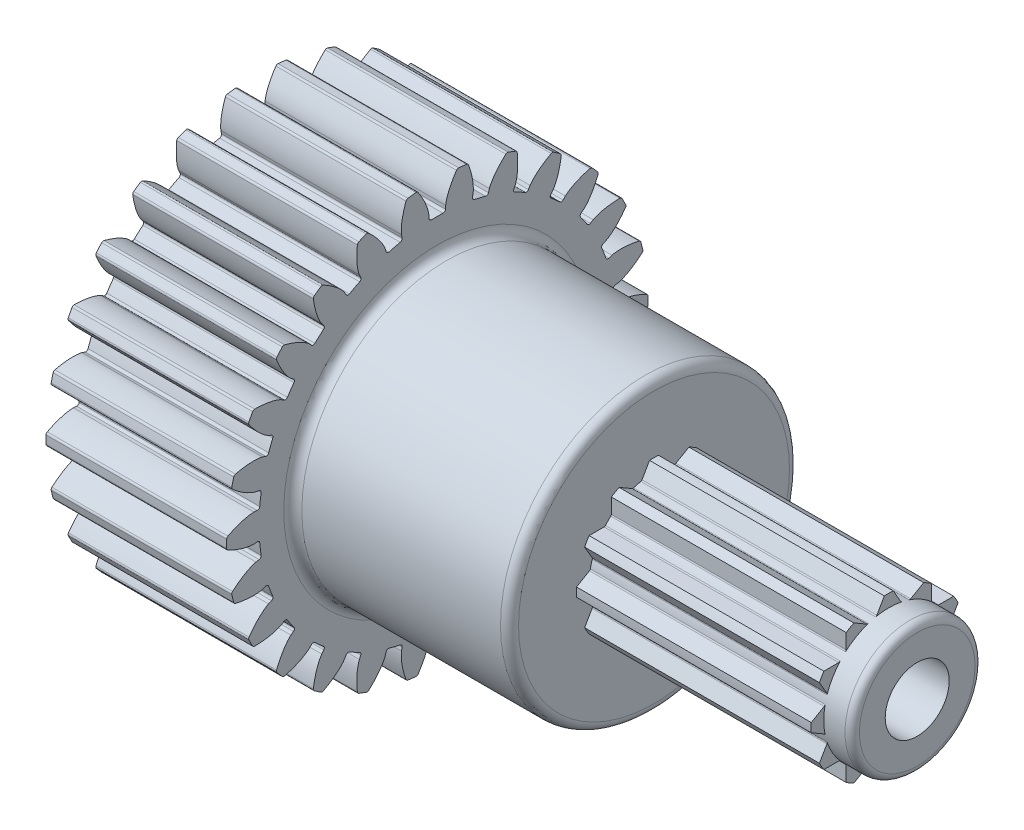
SolidWorks part; units mm, degrees
ref_plane "Front Plane" through (0, 0, 0) normal (1, 0, 0) x (0, 1, 0)
ref_plane "Top Plane" through (0, 0, 0) normal (0, 0, 1) x (0, 1, 0)
ref_plane "Right Plane" through (0, 0, 0) normal (0, 1, 0) x (-1, 0, 0)
sketch "Sketch2" plane through (0, 0, 0) normal (1, 0, 0) x (0, 1, 0)
  circle A0 centre (0, 0) radius 3.9688
  circle A1 centre (0, 0) radius 14.8167
  dimension "D1" = 7.9375
  dimension "D2" = 29.6333
extrude "Gear Width Extrude" add sketch "Sketch2" along normal blind 12.7
sketch "Sketch3" plane through (0, 0, 0) normal (1, 0, 0) x (0, 1, 0)
  line L0 (-14.8167, 0) -> (14.8167, 0) construction
  line L1 (0, 14.8167) -> (0, -14.8167) construction
  line L2 (0, 0) -> (12.9152, 0.5882) construction
  line L5 (12.5338, 0) -> (14.8167, 0)
  line L6 (12.9152, 0.5882) -> (12.5209, 0.5702)
  circle A0 centre (0, 0) radius 12.5338 construction
  circle A1 centre (0, 0) radius 12.9286 construction
  circle A2 centre (0, 0) radius 13.7583 construction
  circle A3 centre (0, 0) radius 14.8167 construction
  arc A7 (14.7499, 1.4052) -> (14.8167, 0) centre (0, 0) cw
  arc A8 (12.5209, 0.5702) -> (12.5338, 0) centre (0, 0) cw
  spline S0 degree 4 poles (12.9152, 0.5882) (12.9182, 0.5884) (12.9266, 0.589) (12.9524, 0.5915) (13.0033, 0.5985) (13.0658, 0.61) (13.1375, 0.6259) (13.2064, 0.6434) (13.2652, 0.6597) (13.3236, 0.6772) (13.3817, 0.6958) (13.4518, 0.7196) (13.5357, 0.7499) (13.6332, 0.788) (13.7433, 0.8343) (13.8548, 0.8849) (13.9641, 0.9373) (14.0738, 0.9935) (14.1795, 1.05) (14.2886, 1.1119) (14.389, 1.1707) (14.5005, 1.2401) (14.5903, 1.2971) (14.7079, 1.376) (14.777, 1.4237) (14.8576, 1.4809) (14.8932, 1.5069) (14.9151, 1.5229) knots 0 0 0 0 0 0.005377 0.015084 0.04661 0.092111 0.119476 0.146842 0.174209 0.201575 0.228941 0.256307 0.307035 0.361767 0.4165 0.471232 0.525964 0.580697 0.635429 0.690161 0.744894 0.799626 0.854358 0.909091 0.954545 1 1 1 1 1 construction
  spline S1 degree 4 poles (12.9152, 0.5882) (12.9182, 0.5884) (12.9266, 0.589) (12.9524, 0.5915) (13.0033, 0.5985) (13.0658, 0.61) (13.1375, 0.6259) (13.2064, 0.6434) (13.2652, 0.6597) (13.3236, 0.6772) (13.3817, 0.6958) (13.4518, 0.7196) (13.5357, 0.7499) (13.6332, 0.788) (13.7433, 0.8343) (13.8548, 0.8849) (13.9641, 0.9373) (14.0738, 0.9935) (14.1795, 1.05) (14.2886, 1.1119) (14.389, 1.1707) (14.5005, 1.2401) (14.5903, 1.2971) (14.6824, 1.3589) (14.7271, 1.3894) (14.7499, 1.4052) knots 0 0 0 0 0 0.005377 0.015084 0.04661 0.092111 0.119476 0.146842 0.174209 0.201575 0.228941 0.256307 0.307035 0.361767 0.4165 0.471232 0.525964 0.580697 0.635429 0.690161 0.744894 0.799626 0.854358 0.909091 0.909091 0.909091 0.909091 0.909091
  dimension "D1" = 27.5167
  dimension "D2" = 25.8572
  dimension "D3" = 25.0677
extrude "Gear Tooth Cut" cut sketch "Sketch3" along normal blind 25.4
mirror "Gear Tooth Cut Mirror" about plane through (25.4, 0, 0) normal (0, 0, 1) of "Gear Tooth Cut"
fillet "Tooth Fillets" radius 0.1662 4 edges at (6.35, 14.7499, 1.4052) (6.35, 14.7499, -1.4052) (6.35, 12.5209, 0.5702) (6.35, 12.5209, -0.5702)
pattern_circular "CirPattern1" count 26 over 360 about axis through (0, 0, 0) along (1, 0, 0) of "Gear Tooth Cut", "Gear Tooth Cut Mirror", "Tooth Fillets"
sketch "Sketch4" plane through (0, 0, 0) normal (0, 1, 0) x (-1, 0, 0)
  line L5 (0, 0) -> (0, 3.9688)
  line L6 (0, 3.9688) -> (-12.7, 3.9687)
  line L7 (-12.7, 3.9687) -> (-12.7, 10.16)
  line L9 (-44.45, 5.461) -> (-44.45, 0)
  line L10 (6.985, 0) -> (-6.985, 0) construction
  line L11 (-44.45, 0) -> (0, 0)
  line L12 (0, 16.2151) -> (0, -16.2151) construction
  line L13 (-12.7, 3.9688) -> (-12.7, -3.9688) construction
  line L14 (-27.94, 10.16) -> (-27.94, 5.461)
  line L15 (-27.94, 5.461) -> (-44.45, 5.461)
  line L16 (-12.7, 10.16) -> (-27.94, 10.16)
  point P0 (0, 3.9688)
  point P1 (-17.6617, 0)
  point P3 (0, 0)
  point P4 (-0.3557, 0)
  point P10 (0, 0)
  point P21 (0, 0)
  point P22 (0, 0)
  point P23 (4.5864, 0)
  point P24 (3.81, 0)
  point P25 (0, 0)
  point P26 (3.81, 0)
  dimension "D2" = 44.45
  dimension "D3" = 10.16
  dimension "D4" = 5.461
  dimension "D5" = 16.51
revolve "Revolve1" add sketch "Sketch4" angle 360 about L11
sketch "Sketch5" plane through (44.45, 0, 0) normal (1, 0, 0) x (0, 1, 0)
  line L0 (0, 5.461) -> (0, 4.572)
  line L2 (-2.9972, 4.565) -> (-2.9972, 3.4525)
  line L3 (2.9972, 4.565) -> (2.9972, 3.4525)
  line L4 (-2.9972, 8.6613) -> (-2.9972, 5.4085) construction
  line L5 (0, 8.6613) -> (0, 5.4085) construction
  line L6 (2.9972, 8.6613) -> (2.9972, 5.4085) construction
  line L7 (2.7305, 4.7294) -> (2.286, 3.9595)
  line L8 (-0.3131, 5.452) -> (-0.8694, 4.4886)
  line L9 (4.8782, 2.4548) -> (4.3219, 1.4914)
  line L10 (4.7294, 2.7305) -> (3.9595, 2.286)
  line L11 (2.4548, 4.8782) -> (1.4914, 4.3219)
  line L12 (5.452, -0.3131) -> (4.4886, -0.8694)
  line L13 (5.461, 0) -> (4.572, 0)
  line L14 (4.565, 2.9972) -> (3.4525, 2.9972)
  line L15 (4.565, -2.9972) -> (3.4525, -2.9972)
  line L16 (4.7294, -2.7305) -> (3.9595, -2.286)
  line L17 (5.452, 0.3131) -> (4.4886, 0.8694)
  line L18 (2.4548, -4.8782) -> (1.4914, -4.3219)
  line L19 (2.7305, -4.7294) -> (2.286, -3.9595)
  line L20 (4.8782, -2.4548) -> (4.3219, -1.4914)
  line L21 (-0.3131, -5.452) -> (-0.8694, -4.4886)
  line L22 (0, -5.461) -> (0, -4.572)
  line L23 (2.9972, -4.565) -> (2.9972, -3.4525)
  line L24 (-2.9972, -4.565) -> (-2.9972, -3.4525)
  line L25 (-2.7305, -4.7294) -> (-2.286, -3.9595)
  line L26 (0.3131, -5.452) -> (0.8694, -4.4886)
  line L27 (-4.8782, -2.4548) -> (-4.3219, -1.4914)
  line L28 (-4.7294, -2.7305) -> (-3.9595, -2.286)
  line L29 (-2.4548, -4.8782) -> (-1.4914, -4.3219)
  line L30 (-5.452, 0.3131) -> (-4.4886, 0.8694)
  line L31 (-5.461, 0) -> (-4.572, 0)
  line L32 (-4.565, -2.9972) -> (-3.4525, -2.9972)
  line L33 (-4.565, 2.9972) -> (-3.4525, 2.9972)
  line L34 (-4.7294, 2.7305) -> (-3.9595, 2.286)
  line L35 (-5.452, -0.3131) -> (-4.4886, -0.8694)
  line L36 (-2.4548, 4.8782) -> (-1.4914, 4.3219)
  line L37 (-2.7305, 4.7294) -> (-2.286, 3.9595)
  line L38 (-4.8782, 2.4548) -> (-4.3219, 1.4914)
  line L39 (0.3131, 5.452) -> (0.8694, 4.4886)
  circle A0 centre (0, 0) radius 5.461
  circle A1 centre (0, 0) radius 4.572
  circle A2 centre (0, 0) radius 5.461 construction
  circle A3 centre (0, 0) radius 5.5
  point P111 (0, 0)
  dimension "D1" = 9.144
  dimension "D2" = 2.9972
  dimension "D3" = 2.9972
  dimension "D4" = 12
extrude "Cut-Extrude1" cut sketch "Sketch5" along direction (-1, 0, 0) on the side against the normal up to surface (16.51 mm away) contours A1 L8 L4 L3 | A1 L11 L4 L9 | A1 L14 L4 L12 | A1 L17 L4 L15 | A1 L20 L4 L18 | A1 L23 L4 L21 | A1 L26 L4 L24 | A1 L29 L4 L27 | A1 L32 L4 L30 | A1 L35 L4 L33 | A1 L38 L4 L36 | A1 L2 L4 L39
fillet "Fillet3" radius 0.635 2 edges at (12.7, 0, -10.16) (27.94, 0, -10.16)
fillet "Fillet5" radius 0.127 24 edges at (36.195, -0.8694, 4.4886) (36.195, 1.4914, 4.3219) (36.195, 2.9972, 3.4525) (36.195, 4.3219, 1.4914) (36.195, 3.4525, 2.9972) (36.195, 4.4886, 0.8694) (36.195, 4.4886, -0.8694) (36.195, 3.4525, -2.9972) (36.195, 4.3219, -1.4914) (36.195, 1.4914, -4.3219) (36.195, 2.9972, -3.4525) (36.195, 0.8694, -4.4886) (36.195, -1.4914, -4.3219) (36.195, -3.4525, -2.9972) (36.195, -3.4525, 2.9972) (36.195, -0.8694, -4.4886) (36.195, -2.9972, -3.4525) (36.195, -4.3219, -1.4914) (36.195, -4.4886, 0.8694) (36.195, -4.4886, -0.8694) (36.195, -1.4914, 4.3219) (36.195, 0.8694, 4.4886) (36.195, -4.3219, 1.4914) (36.195, -2.9972, 3.4525)
sketch "Sketch6" plane through (44.45, 0, 0) normal (1, 0, 0) x (0, 0, -1)
  circle A0 centre (0, 0) radius 4.572
extrude "Boss-Extrude1" add sketch "Sketch6" along normal blind 2
fillet "Fillet6" radius 0.508 1 edges at (46.45, 0, -4.572)
sketch "Sketch7" plane through (0, 0, 0) normal (-1, 0, 0) x (0, -1, 0)
  circle A0 centre (0, 0) radius 2.25
  dimension "D1" = 4.5
extrude "Cut-Extrude2" cut sketch "Sketch7" against normal through all contours A0
sketch "Sketch8" plane through (0, 0, 0) normal (-1, 0, 0) x (0, -1, 0)
  circle A0 centre (0, 0) radius 4
  dimension "D1" = 8
extrude "Cut-Extrude3" cut sketch "Sketch8" against normal blind 6.35 contours A0
equation "\"DP\"= 24'INPUT: Diametral Pitch"
equation "\"a_Pressure\"= 20'INPUT: Pressure Angle"
equation "\"Z\"= 26'INPUT: Number of Teeth"
equation "\"w_Face\"= 0.5'INPUT: Face Width"
equation "\"d_Bore\"= 5 / 16'INPUT: Bore Diameter"
equation "\"d_Pitch\"= \"Z\" / \"DP\"'Pitch Diameter"
equation "\"Module\"= 1 / \"DP\"'Module"
equation "\"d_Base\"= \"d_Pitch\" * cos ( \"a_Pressure\" )'Base Circle Diameter"
equation "\"Clearance\"= 0.157 / \"DP\"'Clearance"
equation "\"CP\"= pi * \"d_Pitch\" / \"Z\"'Circular Pitch"
equation "\"h_Addendum\"= 1 / \"DP\"'Addendum Depth"
equation "\"h_Dedendum\"= IIF ( \"h_deStandard\" > \"h_deMin\" , \"h_deStandard\" , \"h_deMin\" )'Dedendum Depth"
equation "\"d_Addendum\"= \"d_Pitch\" + ( 2 * \"h_Addendum\" )'Addendum (Tip) Diameter"
equation "\"d_Dedendum\"= \"d_Pitch\" - ( 2 * \"h_Dedendum\" )'Dedendum (Root) Diameter"
equation "\"a_Pitch\"= 360 / \"Z\"'Pitch Angle"
equation "\"a_Alpha\"= ( ( 180 * ( ( \"d_Pitch\" ^ 2 ) - ( \"d_Base\" ^ 2 ) ) ^ 0.5 ) / ( pi * \"d_Base\" ) ) - \"a_Pressure\"'Alpha Angle"
equation "\"a_Beta\"= ( \"a_Pitch\" / 4 ) - \"a_Alpha\"'Beta Angle"
equation "\"ICDP\"= ( ( ( \"d_Addendum\" / 2 ) ^ 2 - ( \"d_Base\" / 2 ) ^ 2 ) ^ 0.5 ) * ( 2 / \"d_Base\" )'Involute Curve Domain Parameter"
equation "\"D1@Sketch2\"=\"d_Bore\""
equation "\"D2@Sketch2\"=\"d_Addendum\""
equation "\"D1@Gear Width Extrude\" = \"w_Face\""
equation "\"D1@Sketch3\"=\"d_Pitch\""
equation "\"D2@Sketch3\"=\"d_Base\""
equation "\"D3@Sketch3\"= \"d_Dedendum\""
equation "\"D1@CirPattern1\"=\"Z\""
equation "\"D1@Tooth Fillets\"=\"Clearance\""
equation "\"h_deStandard\"= ( 1 / \"DP\" ) + \"Clearance\""
equation "\"h_deMin\"= ( \"d_Pitch\" * ( 1 - cos ( \"a_Pressure\" ) ) / 2 ) + \"Clearance\""
